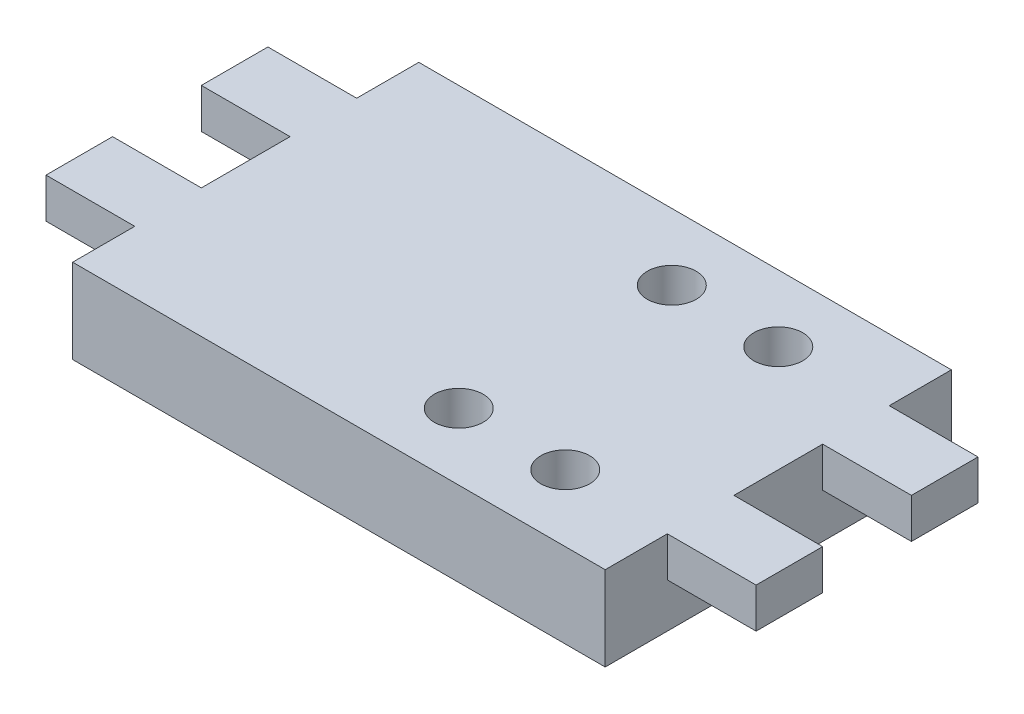
SolidWorks part; units mm, degrees
ref_plane "Front Plane" through (0, 0, 0) normal (0, 0, 1) x (1, 0, 0)
ref_plane "Top Plane" through (0, 0, 0) normal (0, 1, 0) x (1, 0, 0)
ref_plane "Right Plane" through (0, 0, 0) normal (1, 0, 0) x (0, 0, -1)
sketch "Sketch1" plane through (0, 0, 0) normal (1, 0, 0) x (0, 0, -1)
  line L1 (-12.5, -2.25) -> (12.5, -2.25)
  line L2 (-12.5, -2.25) -> (-12.5, 2.25)
  line L3 (-12.5, 2.25) -> (12.5, 2.25)
  line L4 (12.5, -2.25) -> (12.5, 2.25)
  line L5 (-12.5, -2.25) -> (12.5, 2.25) construction
  line L6 (-12.5, 2.25) -> (12.5, -2.25) construction
  point P0 (0, 0)
  dimension "D1" = 4.5
  dimension "D2" = 25
extrude "Boss-Extrude1" add sketch "Sketch1" along normal mid plane 60
sketch "Sketch2" plane through (30, 0, 0) normal (1, 0, 0) x (0, 0, -1)
  line L5 (12.5, 2.25) -> (-12.5, 2.25) construction
  line L6 (-12.5, 2.25) -> (-5, 2.25)
  line L7 (-12.5, 2.25) -> (-12.5, -2.25)
  line L8 (-12.5, -2.25) -> (-5, -2.25)
  line L9 (-5, 2.25) -> (-5, -2.25)
  line L10 (5, 2.25) -> (12.5, 2.25)
  line L11 (5, 2.25) -> (5, -2.25)
  line L12 (5, -2.25) -> (12.5, -2.25)
  line L13 (12.5, 2.25) -> (12.5, -2.25)
  line L14 (-12.5, -2.25) -> (12.5, -2.25) construction
  line L15 (-12.5, 2.25) -> (-12.5, -2.25) construction
  line L16 (12.5, -2.25) -> (12.5, 2.25) construction
  dimension "D1" = 7.5
  dimension "D2" = 7.5
extrude "Boss-Extrude2" add sketch "Sketch2" along normal blind 10
sketch "Esquisse1" plane through (0, 0, 12.5) normal (0, 0, 1) x (1, 0, 0)
  line L0 (40, -2.25) -> (-30, -2.25) construction
  line L1 (-30, 2.25) -> (30, 2.25)
  line L2 (-30, 2.25) -> (-30, -2.25)
  line L3 (-30, -2.25) -> (30, -2.25)
  line L4 (30, 2.25) -> (30, -2.25)
  dimension "D1" = 60
extrude "Boss.-Extru.1" add sketch "Esquisse1" along normal blind 7
mirror "Symétrie1" about plane through (0, 0, 0) normal (0, 0, 1) of "Boss.-Extru.1"
mirror "Mirror1" about plane through (0, 0, 0) normal (1, 0, 0) of "Boss-Extrude2"
sketch "Sketch6" plane through (0, -2.25, 0) normal (0, -1, 0) x (1, 0, 0)
  line L0 (-30, 19.5) -> (-30, -19.5)
  line L1 (-30, -19.5) -> (30, -19.5)
  line L2 (30, -19.5) -> (30, 19.5)
  line L3 (30, 19.5) -> (-30, 19.5)
extrude "Boss-Extrude3" add sketch "Sketch6" along normal blind 5
hole_wizard "CBORE for M3 SBHCS2" positions "Sketch4" profile "Sketch5" counterbore size "M3" standard "ANSI Metric" end condition through all
sketch "Sketch4" plane through (0, 2.25, 0) normal (0, -1, 0) x (-1, 0, 0)
  line L0 (-18, 12) -> (-18, -12) construction
  line L1 (-18, -12) -> (-6, -12) construction
  line L2 (-6, -12) -> (-6, 12) construction
  line L3 (-6, 12) -> (-18, 12) construction
  line L4 (-30, 19.5) -> (-30, -19.5) construction
  point P0 (-18, 12)
  point P3 (-6, 12)
  point P6 (-6, -12)
  point P9 (-18, -12)
  point P12 (-18, 12)
  point P13 (-18, -12)
  point P14 (-6, -12)
  point P15 (-6, 12)
  point P18 (-6, 0)
  point P21 (-14.8638, 12)
  dimension "D1" = 12
  dimension "D2" = 24
  dimension "D3" = 12
sketch "Sketch5" plane through (18, 2.25, -12) normal (1, 0, 0) x (0, 0, 1)
  line L0 (0, 0) -> (0, 9.5)
  line L1 (0, 9.5) -> (1.4, 9.5)
  line L3 (1.4, 9.5) -> (1.4, 8.1)
  line L4 (1.4, 8.1) -> (2.75, 8.1)
  line L5 (2.75, 8.1) -> (2.75, 0)
  line L7 (2.75, 0) -> (0, 0)
  line L11 (0, -6.35) -> (0, 107.95) construction
  dimension "Thru Hole Dia." = 2.8
  dimension "Thru Hole Depth" = 9.5
  dimension "C'Bore Dia." = 5.5
  dimension "C'Bore Depth" = 8.1
